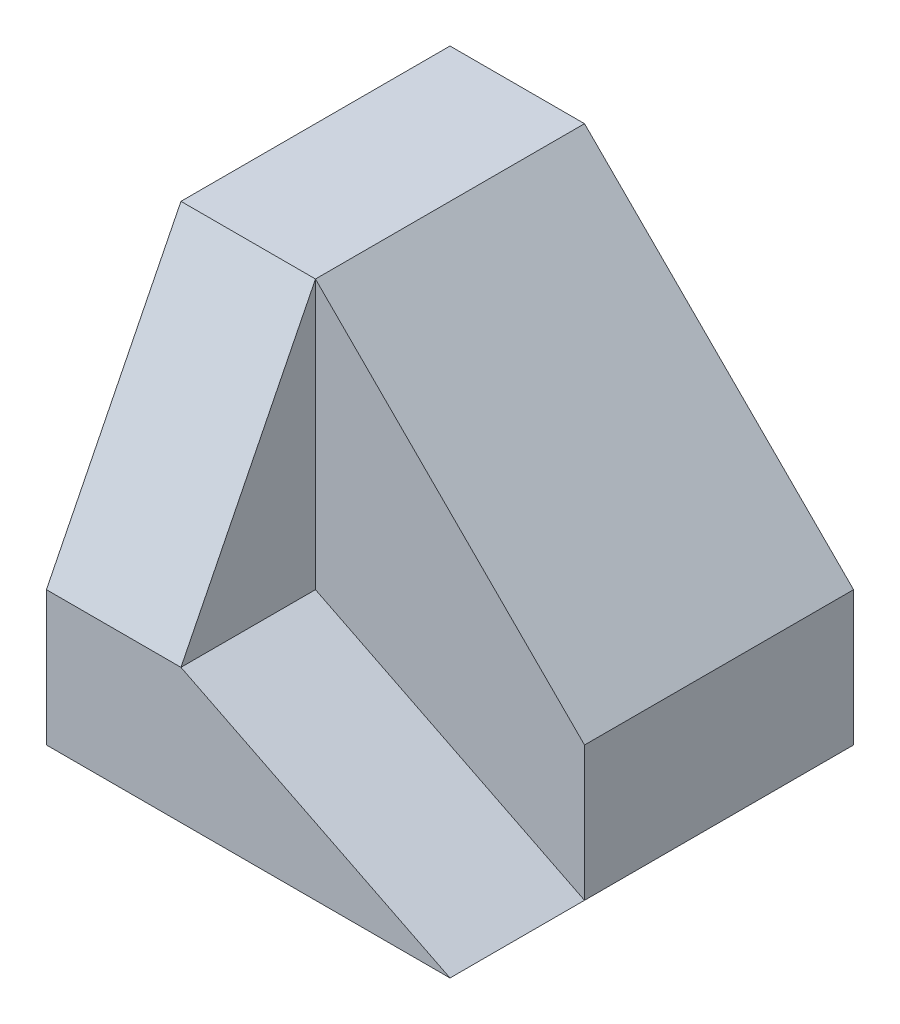
SolidWorks part; units mm, degrees
ref_plane "Alzado" through (0, 0, 0) normal (0, 0, 1) x (1, 0, 0)
ref_plane "Planta" through (0, 0, 0) normal (0, 1, 0) x (1, 0, 0)
ref_plane "Vista lateral" through (0, 0, 0) normal (1, 0, 0) x (0, 0, -1)
sketch "Croquis1" plane through (0, 0, 0) normal (0, 1, 0) x (1, 0, 0)
  line L0 (-10, -30) -> (-10, -10)
  line L1 (30, 30) -> (-30, 30)
  line L2 (30, 30) -> (30, -10)
  line L3 (-10, -30) -> (-30, -30)
  line L4 (-30, 30) -> (-30, -30)
  line L5 (30, 30) -> (-30, -30) construction
  line L6 (30, -30) -> (-30, 30) construction
  line L7 (-10, -10) -> (30, -10)
  point P0 (0, 0)
  dimension "D1" = 60
  dimension "D2" = 60
  dimension "D3" = 40
  dimension "D4" = 20
  dimension "D5" = 30
extrude "Saliente-Extruir3" add sketch "Croquis1" along normal blind 60
chamfer "Chaflán1" distance 40 distance2 40 1 edges at (30, 60, -10)
chamfer "Chaflán2" distance 40 distance2 20 1 edges at (-20, 60, 30) first distance on face at (-20, 30, 30)
sketch "Croquis3" plane through (0, 0, 0) normal (0, 1, 0) x (1, 0, 0)
  line L0 (-10, -10) -> (30, -10) construction
  line L6 (-10, -30) -> (-10, -10) construction
  line L8 (-10, -10) -> (30, -10)
  line L14 (-10, -30) -> (-10, -10)
  line L16 (-10, -30) -> (30, -30)
  line L17 (30, -30) -> (30, -10)
extrude "Saliente-Extruir4" add sketch "Croquis3" along normal blind 20 contours L17 L16 L14 L8
chamfer "Chaflán3" distance 20 distance2 40 1 edges at (30, 20, 20) first distance on face at (30, 12, 2)
